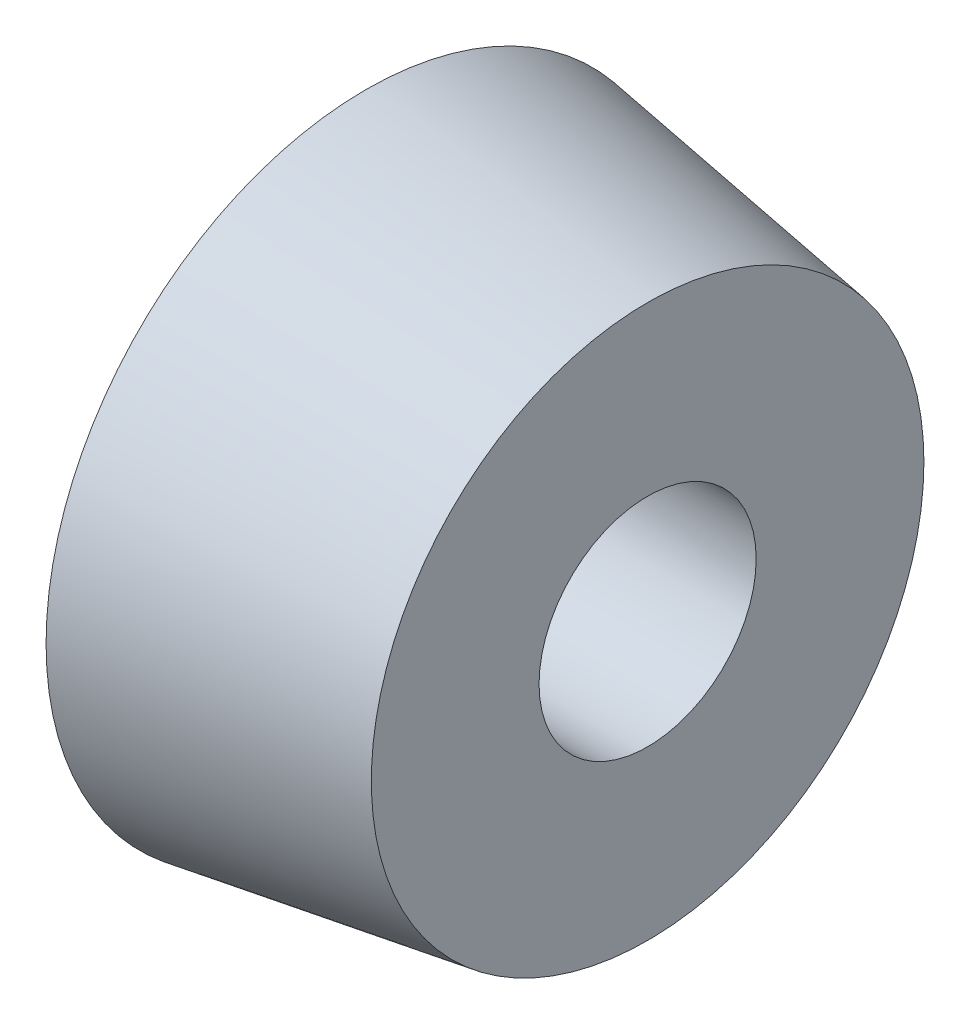
SolidWorks part; units mm, degrees
ref_plane "Front Plane" through (0, 0, 0) normal (0, 0, 1) x (1, 0, 0)
ref_plane "Top Plane" through (0, 0, 0) normal (0, 1, 0) x (1, 0, 0)
ref_plane "Right Plane" through (0, 0, 0) normal (1, 0, 0) x (0, 0, -1)
sketch "Sketch1" plane through (0, 0, 0) normal (0, 1, 0) x (1, 0, 0)
  line L2 (929.7723, 97.8305) -> (929.7723, 76.2)
  line L3 (948.8223, 94.8858) -> (948.8223, 76.2)
  line L4 (929.7723, 97.8305) -> (948.8223, 94.8858)
  line L5 (1049.7211, 76.2) -> (927.1762, 76.2) construction
  line L6 (929.7723, 76.2) -> (948.8223, 76.2)
  spline S0 degree 3 poles (1698.8541, -566.5092) (1513.356, -28.2517) (1211.581, 58.1372) (887.8186, 103.8771) (872.5346, 105.9273) (841.9435, 109.8647) (826.6361, 111.7515) (796.0038, 115.3893) (780.6789, 117.14) (734.683, 122.2143) (703.9913, 125.362) (642.5687, 131.261) (611.8375, 134.0115) (550.3439, 139.1405) (519.5815, 141.5188) (458.0303, 145.8934) (427.2415, 147.8905) (381.0416, 150.5596) (365.6389, 151.3944) (334.8283, 152.9394) (319.4206, 153.6499) (288.6013, 154.919) (273.1897, 155.4794) (250.0725, 156.1593) (242.3667, 156.3596) (230.8108, 156.6017) (226.9593, 156.6726) (99.3596, 158.5747) (-23.9566, 150.7789) (346.5117, -833.9102) knots -1.200454 -1.200454 -1.200454 -1.200454 0.0625 0.0625 0.125 0.125 0.1875 0.1875 0.25 0.25 0.375 0.375 0.5 0.5 0.625 0.625 0.75 0.75 0.8125 0.8125 0.875 0.875 0.9375 0.9375 0.96875 0.96875 0.984375 0.984375 1.48656 1.48656 1.48656 1.48656 only from (948.8223, 94.8858) to (211.5741, 156.845) construction
  spline S1 degree 3 poles (948.8223, 94.8858) (933.6019, 97.3018) (918.3518, 99.5635) (887.8186, 103.8771) (872.5346, 105.9273) (841.9435, 109.8647) (826.6361, 111.7515) (796.0038, 115.3893) (780.6789, 117.14) (734.683, 122.2143) (703.9913, 125.362) (642.5687, 131.261) (611.8375, 134.0115) (550.3439, 139.1405) (519.5815, 141.5188) (458.0303, 145.8934) (427.2415, 147.8905) (381.0416, 150.5596) (365.6389, 151.3944) (334.8283, 152.9394) (319.4206, 153.6499) (288.6013, 154.919) (273.1897, 155.4794) (250.0725, 156.1593) (242.3667, 156.3596) (230.8108, 156.6017) (226.9593, 156.6726) (219.2586, 156.7873) (215.4087, 156.8354) (211.5741, 156.845) knots 0 0 0 0 0.0625 0.0625 0.125 0.125 0.1875 0.1875 0.25 0.25 0.375 0.375 0.5 0.5 0.625 0.625 0.75 0.75 0.8125 0.8125 0.875 0.875 0.9375 0.9375 0.96875 0.96875 0.984375 0.984375 1 1 1 1 construction
  point P2 (0, 0)
  point P5 (1049.7211, 76.2)
  dimension "D1" = 19.05
revolve "Revolve2" add sketch "Sketch1" angle 360 about L5
hole_wizard "Tap Drill for 9/16 Helicoil0" positions "Sketch2" profile "Sketch3" hole size "9/16-12" standard "ANSI Inch" end condition through all
sketch "Sketch2" plane through (929.7723, 0, 0) normal (-1, 0, 0) x (0, 0, 1)
  circle A3 centre (-76.2, 0) radius 21.6305
  circle A4 centre (-76.2, 0) radius 21.6305 construction
  point P0 (-76.2, 0)
  dimension "D1" = 0
sketch "Sketch3" plane through (929.7723, 0, -76.2) normal (0, 1, 0) x (0, 0, 1)
  line L0 (0, 0) -> (0, 19.05)
  line L1 (0, 19.05) -> (7.3419, 19.05)
  line L2 (7.3419, 19.05) -> (7.3419, 0)
  line L5 (7.3419, 0) -> (0, 0)
  line L11 (0, -6.35) -> (0, 107.95) construction
  dimension "Thru Hole Dia." = 14.6837
  dimension "Thru Hole Depth" = 19.05
sketch "Sketch4" plane through (929.7723, 0, 0) normal (-1, 0, 0) x (0, 0, 1)
  circle A0 centre (-76.2, 0) radius 10.3187
  circle A1 centre (-76.2, 0) radius 19.05
  dimension "D1" = 20.6375
  dimension "D2" = 38.1
extrude "Cut-Extrude1" [suppressed] cut sketch "Sketch4" against normal blind 12.7 draft 10
fillet "Fillet1" [suppressed] radius 3.175
sketch "Sketch5" plane through (0, 0, 0) normal (0, 1, 0) x (1, 0, 0)
  line L1 (927.6092, 95.5947) -> (927.6092, 86.0819)
  line L2 (927.6092, 95.5947) -> (943.5923, 93.1241)
  line L5 (946.2823, 89.9863) -> (946.2823, 89.2569)
  line L6 (943.1073, 86.0819) -> (927.6092, 86.0819)
  line L7 (948.8223, 94.8858) -> (929.7723, 97.8305) construction
  line L8 (948.8223, 94.8858) -> (929.7723, 97.8305) construction
  line L9 (948.8223, 83.5419) -> (929.7723, 83.5419) construction
  line L10 (948.8223, 83.5419) -> (929.7723, 83.5419) construction
  line L12 (1049.7211, 76.2) -> (913.4307, 76.2) construction
  arc A0 (946.2823, 89.2569) -> (943.1073, 86.0819) centre (943.1073, 89.2569) cw
  arc A1 (943.5923, 93.1241) -> (946.2823, 89.9863) centre (943.1073, 89.9863) cw
  point P14 (946.2823, 92.7083)
  dimension "D5" = 3.175
  dimension "D2" = 2.54
  dimension "D4" = 2.54
  dimension "D1" = 2.54
revolve "Cut-Revolve1" cut sketch "Sketch5" angle 360 about L12
